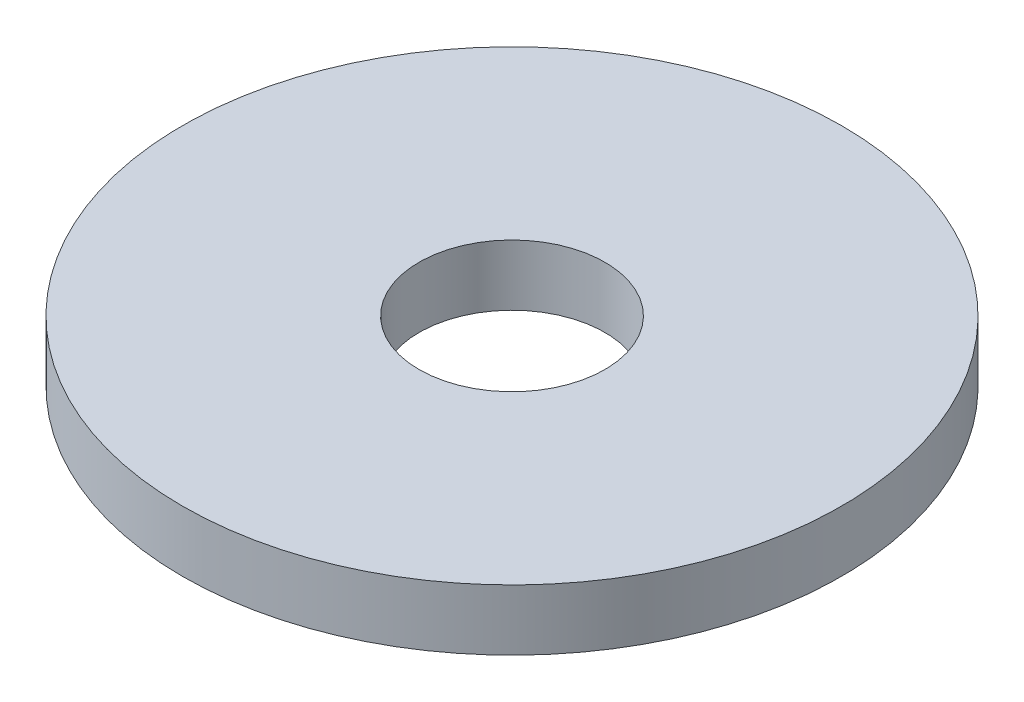
SolidWorks part; units mm, degrees
ref_plane "Front Plane" through (0, 0, 0) normal (0, 0, 1) x (1, 0, 0)
ref_plane "Top Plane" through (0, 0, 0) normal (0, 1, 0) x (1, 0, 0)
ref_plane "Right Plane" through (0, 0, 0) normal (1, 0, 0) x (0, 0, -1)
sketch "Sketch1" plane through (0, 0, 0) normal (0, 1, 0) x (1, 0, 0)
  circle A0 centre (0, 0) radius 97.5
  dimension "FLANGE_OD" = 195
extrude "Boss-Extrude1" add sketch "Sketch1" along normal blind 18
sketch "Sketch2" plane through (0, 0, 0) normal (0, 1, 0) x (1, 0, 0)
  circle A0 centre (0, 0) radius 27.5
  dimension "BORE_D" = 55
extrude "Cut-Extrude1" cut sketch "Sketch2" along normal through all
sketch "Sketch3" plane through (0, 18, 0) normal (0, 1, 0) x (1, 0, 0)
  circle A0 centre (0, 0) radius 22.1102 construction
  circle A1 centre (-22.1102, 0) radius 5.3258
  dimension "BOLT_D" = 10.6516
  dimension "BOLT_PCD" = 44.2203
extrude "Cut-Extrude2" cut sketch "Sketch3" against normal blind 13.2938 rebuild error yes
pattern_circular "CirPattern1" count 4 over 360 rebuild error yes
